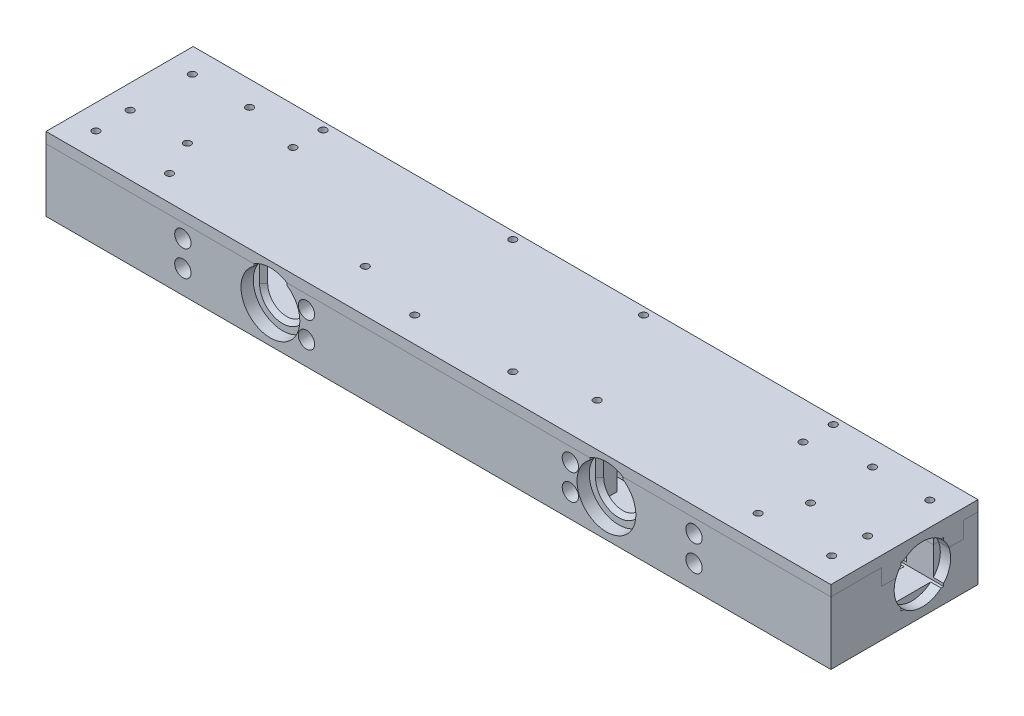
SolidWorks part; units mm, degrees
other "Bee-zerker Body Wedge"
other "Cam Body"
other "Cam Top Plate"
material "PLA/ABS"
ref_plane "Front Plane" through (0, 0, 0) normal (0, 0, 1) x (1, 0, 0)
ref_plane "Top Plane" through (0, 0, 0) normal (0, 1, 0) x (1, 0, 0)
ref_plane "Right Plane" through (0, 0, 0) normal (1, 0, 0) x (0, 0, -1)
sketch "Sketch1" plane through (0, 0, 0) normal (0, 1, 0) x (1, 0, 0)
  line L0 (-110.49, 0) -> (0, 0) construction
  line L1 (-152.4, -35.56) -> (152.4, -35.56)
  line L2 (-152.4, -35.56) -> (-152.4, 21.59)
  line L3 (-152.4, 21.59) -> (152.4, 21.59)
  line L4 (152.4, -35.56) -> (152.4, 21.59)
  line L5 (-152.4, -35.56) -> (152.4, 21.59) construction
  line L6 (-152.4, 21.59) -> (152.4, -35.56) construction
  line L11 (0, 0) -> (0, -6.985) construction
  line L12 (-65.25, 10.79) -> (-65.25, -35.56) construction
  line L13 (-110.49, 0) -> (-171.45, 0) construction
  line L14 (-110.49, -10.9728) -> (-152.4, -10.9728)
  line L15 (-110.49, -10.9728) -> (-110.49, 10.9728)
  line L16 (-110.49, 10.9728) -> (-152.4, 10.9728)
  line L17 (-152.4, -10.9728) -> (-152.4, 10.9728)
  line L18 (-110.49, -10.9728) -> (-152.4, 10.9728) construction
  line L19 (-110.49, 10.9728) -> (-152.4, -10.9728) construction
  line L20 (-45.725, -0.1905) -> (7.9198, -0.1905)
  line L21 (-45.725, -0.1905) -> (-45.725, 16.8275)
  line L22 (-45.725, 16.8275) -> (7.9198, 16.8275)
  line L23 (7.9198, -0.1905) -> (7.9198, 16.8275)
  line L24 (-45.725, -0.1905) -> (7.9198, 16.8275) construction
  line L25 (-45.725, 16.8275) -> (7.9198, -0.1905) construction
  line L26 (-95.25, 10.79) -> (-55.25, 10.79)
  line L27 (-95.25, 10.79) -> (-95.25, -29.21)
  line L28 (-95.25, -29.21) -> (-55.25, -29.21)
  line L29 (-55.25, 10.79) -> (-55.25, -29.21)
  line L30 (-95.25, 10.79) -> (-55.25, -29.21) construction
  line L31 (-95.25, -29.21) -> (-55.25, 10.79) construction
  point P0 (0, -6.985)
  point P12 (-75.25, -9.21)
  point P13 (-131.445, 0)
  point P19 (-18.9026, 8.3185)
  dimension "D1" = 304.8
  dimension "D2" = 57.15
  dimension "D3" = 21.59
  dimension "D4" = 40
  dimension "D5" = 17.018
  dimension "D6" = 41.91
  dimension "D7" = 21.9456
  dimension "D8" = 19.05
  dimension "D9" = 53.6448
  dimension "D10" = 40
  dimension "D11" = 57.15
  dimension "D12" = 6.35
  dimension "D13" = 4.7625
  dimension "D14" = 9.525
  dimension "D15" = 10
sketch "Sketch2" plane through (0, 0, 0) normal (1, 0, 0) x (0, 0, -1)
  line L0 (-35.56, 11.1125) -> (-35.56, 39.6875)
  line L1 (-35.56, 39.6875) -> (21.59, 39.6875)
  line L2 (21.59, 39.6875) -> (21.59, 11.1125)
  line L3 (21.59, 11.1125) -> (-35.56, 11.1125)
  line L4 (-53.2447, 0) -> (-13.764, 0) construction
  line L5 (0, 25.4) -> (21.59, 25.4) construction
  line L6 (-35.56, 25.4) -> (0, 25.4) construction
  line L7 (-32.5269, 35.56) -> (49967.4731, 35.56) construction
  line L8 (-34.7846, 15.24) -> (49965.2154, 15.24) construction
  line L9 (21.59, 35.56) -> (0, 25.4) construction
  line L10 (0, 25.4) -> (21.59, 15.24) construction
  line L12 (-120.0634, 50.8) -> (-69.9767, 50.8) construction
  circle A0 centre (0, 25.4) radius 25.4
  circle A2 centre (0, 25.4) radius 10.9728
  point P9 (10.9728, 25.4)
  dimension "D1" = 50.8
  dimension "D2" = 28.575
  dimension "D3" = 20.32
sketch "Sketch3" plane through (0, 0, 0) normal (1, 0, 0) x (0, 0, -1)
  line L0 (-35.56, 11.1125) -> (-35.56, 39.6875)
  line L1 (-35.56, 39.6875) -> (21.59, 39.6875)
  line L2 (21.59, 39.6875) -> (21.59, 11.1125)
  line L3 (21.59, 11.1125) -> (-35.56, 11.1125)
extrude "Boss-Extrude1" add sketch "Sketch3" along normal up to vertex (152.4 mm away) and the other way up to vertex (152.4 mm away) up to point (152.4, 0, -21.59) other way up to point (-152.4, 0, -21.59)
sketch "Sketch6" plane through (152.4, 0, 0) normal (1, 0, 0) x (0, 0, -1)
  line L1 (-8.255, 33.655) -> (8.255, 33.655)
  line L2 (-8.255, 33.655) -> (-8.255, 17.145)
  line L3 (-8.255, 17.145) -> (8.255, 17.145)
  line L4 (8.255, 33.655) -> (8.255, 17.145)
  line L5 (-8.255, 33.655) -> (8.255, 17.145) construction
  line L6 (-8.255, 17.145) -> (8.255, 33.655) construction
  point P0 (0, 25.4)
  dimension "D1" = 16.51
extrude "Cut-Extrude2" cut sketch "Sketch6" against normal blind 16.9164
sketch "Sketch7" plane through (152.4, 0, 0) normal (1, 0, 0) x (0, 0, -1)
  circle A0 centre (0, 25.4) radius 10.9728 construction
  circle A1 centre (0, 25.4) radius 10.9728
extrude "Cut-Extrude3" cut sketch "Sketch7" against normal blind 4.0132
sketch "Sketch8" plane through (135.4836, 0, 0) normal (1, 0, 0) x (0, 0, -1)
  circle A0 centre (0, 25.4) radius 10.9728 construction
  circle A1 centre (0, 25.4) radius 10.9728
extrude "Cut-Extrude4" cut sketch "Sketch8" along normal blind 2.54
sketch "Sketch9" plane through (135.4836, 0, 0) normal (1, 0, 0) x (0, 0, -1)
  line L0 (7.7495, 32.0331) -> (7.7495, 18.7669)
  line L1 (-7.7495, 18.7669) -> (-7.7495, 32.0331)
  line L2 (-7.7495, 25.4) -> (7.7495, 25.4) construction
  arc A0 (7.7495, 32.0331) -> (-7.7495, 32.0331) centre (0, 25.4) ccw
  arc A1 (-7.7495, 18.7669) -> (7.7495, 18.7669) centre (0, 25.4) ccw
  dimension "D1" = 20.4013
  dimension "D2" = 15.4991
extrude "Cut-Extrude5" cut sketch "Sketch9" against normal blind 25.4
mirror "Mirror1" of "Cut-Extrude2", "Cut-Extrude3", "Cut-Extrude4", "Cut-Extrude5"
extrude "Cut-Extrude6" cut sketch "Sketch10" against normal up to surface (110.0836 mm away)
sketch "Sketch10" plane through (110.0836, 0, 0) normal (1, 0, 0) x (0, 0, -1)
  line L1 (-9.525, 33.1495) -> (9.525, 33.1495)
  line L2 (-9.525, 33.1495) -> (-9.525, 17.6505)
  line L3 (-9.525, 17.6505) -> (9.525, 17.6505)
  line L4 (9.525, 33.1495) -> (9.525, 17.6505)
  line L5 (-9.525, 33.1495) -> (9.525, 17.6505) construction
  line L6 (-9.525, 17.6505) -> (9.525, 33.1495) construction
  point P0 (0, 25.4)
  dimension "D1" = 19.05
  dimension "D2" = 15.4991
sketch "Sketch11" plane through (0, 0, 0) normal (1, 0, 0) x (0, 0, -1)
  line L0 (-35.56, 39.6875) -> (-35.56, 11.1125) construction
  line L1 (21.59, 39.6875) -> (-35.56, 39.6875) construction
  line L2 (-35.56, 35.56) -> (-15.875, 35.56)
  line L3 (-15.875, 35.56) -> (-15.875, 29.21)
  line L4 (-15.875, 29.21) -> (0, 29.21)
  line L5 (15.875, 29.21) -> (15.875, 35.56)
  line L6 (15.875, 35.56) -> (21.59, 35.56)
  line L9 (0, 11.1125) -> (0, 39.6875) construction
  line L10 (-35.56, 11.1125) -> (21.59, 11.1125) construction
  line L12 (0, 29.21) -> (15.875, 29.21)
  line L13 (-35.56, 11.1125) -> (-35.56, 39.6875) construction
  line L14 (-200032.5269, 35.56) -> (249967.4731, 35.56) construction
  dimension "D1" = 10.4775
  dimension "D4" = 15.875
split "Split1" trim tools "Sketch11" bodies to split 113 resulting bodies 178 179
sketch "Sketch13" plane through (0, 11.1125, 0) normal (0, 1, 0) x (1, 0, 0)
  line L1 (-102.87, -15.875) -> (-102.87, 10.79)
  line L3 (-110.0836, 15.875) -> (110.0836, 15.875)
  line L5 (-102.87, 10.79) -> (-95.25, 10.79)
  line L7 (110.0836, 15.875) -> (110.0836, -15.875)
  line L8 (-152.4, -15.875) -> (152.4, -15.875) construction
  line L10 (-152.4, -15.875) -> (152.4, -15.875) construction
  line L12 (-95.25, 10.79) -> (-95.25, -29.21)
  line L16 (-110.0836, -15.875) -> (-110.0836, 15.875)
  line L18 (-110.0836, 7.7495) -> (-110.0836, -7.7495) construction
  line L19 (-152.4, 15.875) -> (152.4, 15.875) construction
  line L21 (-55.25, -29.21) -> (-55.25, 10.79)
  line L23 (-55.25, 10.79) -> (-47.63, 10.79)
  line L24 (-110.0836, -15.875) -> (-102.87, -15.875)
  line L25 (0, -15.875) -> (0, 0) construction
  line L27 (-47.63, 10.79) -> (-47.63, -15.875)
  line L28 (-95.25, -29.21) -> (-55.25, -29.21)
  line L29 (-47.63, -15.875) -> (47.63, -15.875)
  line L30 (47.63, -15.875) -> (47.63, 10.79)
  line L31 (47.63, 10.79) -> (55.25, 10.79)
  line L32 (55.25, 10.79) -> (55.25, -29.21)
  line L33 (95.25, -29.21) -> (95.25, 10.79)
  line L35 (95.25, 10.79) -> (102.87, 10.79)
  line L36 (102.87, 10.79) -> (102.87, -15.875)
  line L37 (55.25, -29.21) -> (95.25, -29.21)
  line L38 (102.87, -15.875) -> (110.0836, -15.875)
  line L39 (110.0836, -7.7495) -> (110.0836, 7.7495) construction
  line L40 (-152.4, -15.875) -> (152.4, -15.875) construction
  line L41 (-95.25, 10.79) -> (-95.25, -29.21) construction
  dimension "D1" = 7.62
extrude "Cut-Extrude7" cut sketch "Sketch13" along normal up to surface (20.32 mm away) from vertex at 4.1275 up to face at (0, 35.56, 25.7175) starting at point (0, 15.24, -21.59)
sketch "Sketch15" plane through (0, 0, 35.56) normal (0, 0, 1) x (1, 0, 0)
  line L0 (-95.25, 15.24) -> (-55.25, 15.24) construction
  line L1 (-95.25, 15.24) -> (-55.25, 15.24) construction
  line L2 (-71.7, 25.24) -> (-71.7, 35.56)
  line L3 (152.4, 35.56) -> (-152.4, 35.56) construction
  line L4 (-71.7, 35.56) -> (-58.8, 35.56)
  line L5 (-58.8, 35.56) -> (-58.8, 25.24)
  arc A0 (-71.7, 25.24) -> (-58.8, 25.24) centre (-65.25, 25.24) ccw
  arc A1 (-58.8, 25.24) -> (-71.7, 25.24) centre (-65.25, 25.24) ccw construction
  dimension "D1" = 12.9
  dimension "D2" = 10
extrude "Cut-Extrude8" cut sketch "Sketch15" against normal up to next (6.35 mm away)
sketch "Sketch16" plane through (0, 35.56, 0) normal (0, 1, 0) x (1, 0, 0)
  line L0 (-95.25, 10.79) -> (-95.25, -29.21) construction
  line L1 (-95.25, -21.49) -> (-102.4, -21.49)
  line L2 (-95.25, -21.49) -> (-95.25, -16.41)
  line L3 (-95.25, -16.41) -> (-102.4, -16.41)
  line L4 (-102.4, -21.49) -> (-102.4, -16.41)
  line L5 (-95.25, -21.49) -> (-102.4, -16.41) construction
  line L6 (-95.25, -16.41) -> (-102.4, -21.49) construction
  line L7 (-55.25, 10.79) -> (-55.25, -29.21) construction
  line L8 (-55.25, -21.49) -> (-48.1, -21.49)
  line L9 (-55.25, -21.49) -> (-55.25, -16.41)
  line L10 (-55.25, -16.41) -> (-48.1, -16.41)
  line L11 (-48.1, -21.49) -> (-48.1, -16.41)
  line L12 (-55.25, -21.49) -> (-48.1, -16.41) construction
  line L13 (-55.25, -16.41) -> (-48.1, -21.49) construction
  line L14 (-95.25, 10.79) -> (-55.25, 10.79) construction
  point P4 (-98.825, -18.95)
  point P11 (-51.675, -18.95)
  dimension "D1" = 27.2
  dimension "D2" = 7.15
  dimension "D3" = 5.08
extrude "Cut-Extrude9" cut sketch "Sketch16" against normal up to surface (20.32 mm away) up to face at (0, 15.24, 3.9175)
sketch "Sketch17" plane through (0, 29.21, 0) normal (0, 1, 0) x (1, 0, 0)
  line L1 (-102.87, -15.875) -> (-95.25, -15.875)
  line L2 (-102.87, -15.875) -> (-102.87, 10.79)
  line L3 (-102.87, 10.79) -> (-95.25, 10.79)
  line L4 (-95.25, -15.875) -> (-95.25, 10.79)
  line L5 (-102.87, -15.875) -> (-95.25, 10.79) construction
  line L6 (-102.87, 10.79) -> (-95.25, -15.875) construction
  line L7 (-47.63, -15.875) -> (-55.25, -15.875)
  line L8 (-47.63, -15.875) -> (-47.63, 10.79)
  line L9 (-47.63, 10.79) -> (-55.25, 10.79)
  line L10 (-55.25, -15.875) -> (-55.25, 10.79)
  line L11 (-47.63, -15.875) -> (-55.25, 10.79) construction
  line L12 (-47.63, 10.79) -> (-55.25, -15.875) construction
  point P4 (-99.06, -2.5425)
  point P11 (-51.44, -2.5425)
extrude "Boss-Extrude2" add sketch "Sketch17" along normal up to surface (6.35 mm away) up to face at (12.2143, 35.56, 23.3757)
sketch "Sketch18" plane through (0, 15.24, 0) normal (0, 1, 0) x (1, 0, 0)
  line L0 (110.0836, 15.875) -> (-110.0836, 15.875) construction
  line L1 (-102.87, 10.79) -> (-47.63, 10.79)
  line L2 (-102.87, 10.79) -> (-102.87, 15.875)
  line L3 (-102.87, 15.875) -> (-47.63, 15.875)
  line L4 (-47.63, 10.79) -> (-47.63, 15.875)
  line L5 (-102.87, 10.79) -> (-47.63, 15.875) construction
  line L6 (-102.87, 15.875) -> (-47.63, 10.79) construction
  line L7 (-55.25, 10.79) -> (-47.63, 10.79) construction
  line L8 (-55.25, 10.79) -> (-47.63, 10.79) construction
  point P4 (-75.25, 13.3325)
extrude "Boss-Extrude3" add sketch "Sketch18" along normal blind 9.525
sketch "Sketch19" plane through (-55.25, 0, 0) normal (-1, 0, 0) x (0, 0, 1)
  line L0 (-10.79, 21.59) -> (-2.79, 21.59)
  line L1 (-10.79, 24.765) -> (-10.79, 15.24) construction
  line L2 (-2.79, 21.59) -> (-2.79, 29.21)
  line L3 (-2.79, 29.21) -> (-10.79, 29.21)
  line L5 (-10.79, 29.21) -> (-10.79, 21.59)
  line L6 (16.41, 15.24) -> (-10.79, 15.24) construction
  line L8 (16.41, 25.4) -> (-2.79, 25.4) construction
  line L9 (16.41, 15.24) -> (16.41, 35.56) construction
  dimension "D1" = 6.35
  dimension "D3" = 8
extrude "Cut-Extrude10" cut sketch "Sketch19" against normal up to surface (7.62 mm away) up to face at (-47.63, 32.385, 2.5425)
sketch "Sketch20" plane through (0, 0, 35.56) normal (0, 0, 1) x (1, 0, 0)
  line L0 (-55.25, 15.24) -> (-48.1, 15.24) construction
  line L1 (-48.1, 15.24) -> (-48.1, 35.56) construction
  line L2 (-48.1, 35.56) -> (-55.25, 35.56) construction
  line L3 (-55.25, 35.56) -> (-55.25, 15.24) construction
  line L4 (-102.4, 15.24) -> (-95.25, 15.24) construction
  line L5 (-95.25, 15.24) -> (-95.25, 35.56) construction
  line L6 (-95.25, 35.56) -> (-102.4, 35.56) construction
  line L7 (-102.4, 35.56) -> (-102.4, 15.24) construction
  line L8 (-55.25, 15.24) -> (-48.1, 15.24) construction
  line L9 (-48.1, 15.24) -> (-48.1, 35.56) construction
  line L10 (-48.1, 35.56) -> (-55.25, 35.56) construction
  line L11 (-55.25, 35.56) -> (-55.25, 15.24) construction
  line L12 (-102.4, 15.24) -> (-95.25, 15.24) construction
  line L13 (-95.25, 15.24) -> (-95.25, 35.56) construction
  line L14 (-95.25, 35.56) -> (-102.4, 35.56) construction
  line L15 (-102.4, 35.56) -> (-102.4, 15.24) construction
  line L16 (-99.25, 20.24) -> (-99.25, 30.24) construction
  line L17 (-51.25, 20.24) -> (-51.25, 30.24) construction
  line L18 (-99.25, 25.24) -> (-95.25, 25.24) construction
  line L20 (-95.25, 25.24) -> (-65.25, 25.24) construction
  line L21 (-65.25, 25.24) -> (-55.25, 25.24) construction
  line L22 (-55.25, 25.24) -> (-51.25, 25.24) construction
  circle A0 centre (-99.25, 20.24) radius 3.175
  circle A1 centre (-99.25, 30.24) radius 3.175
  circle A2 centre (-51.25, 20.24) radius 3.175
  circle A3 centre (-51.25, 30.24) radius 3.175
  circle A4 centre (-65.25, 25.24) radius 6.45 construction
  circle A5 centre (-65.25, 25.24) radius 6.45 construction
  dimension "D2" = 6.35
  dimension "D1" = 4
  dimension "D3" = 10
extrude "Cut-Extrude11" cut sketch "Sketch20" against normal up to surface (19.15 mm away) up to face at (-98.825, 25.4, 16.41)
sketch "Sketch21" plane through (0, 0, 16.41) normal (0, 0, 1) x (1, 0, 0)
  circle A0 centre (-99.25, 30.24) radius 1.397
  circle A1 centre (-99.25, 20.24) radius 1.397
  circle A2 centre (-51.25, 20.24) radius 1.397
  circle A3 centre (-51.25, 30.24) radius 1.397
  dimension "D1" = 2.794
extrude "Cut-Extrude12" cut sketch "Sketch21" against normal blind 25.4
sketch "Sketch28" plane through (0, 0, 35.56) normal (0, 0, 1) x (1, 0, 0)
  circle A0 centre (-65.25, 25.24) radius 11.43
  dimension "D1" = 22.86
extrude "Cut-Extrude16" cut sketch "Sketch28" against normal blind 4.7625
mirror "Mirror2" about plane through (0, 0, 0) normal (1, 0, 0) of "Cut-Extrude16", "Cut-Extrude12", "Cut-Extrude11", "Cut-Extrude10", "Boss-Extrude3", "Boss-Extrude2", "Cut-Extrude9", "Cut-Extrude8"
sketch "Sketch23" plane through (0, 35.56, 0) normal (0, 1, 0) x (1, 0, 0)
  line L0 (-102.87, -15.875) -> (-102.87, 15.875) construction
  line L1 (-110.0836, -15.875) -> (-102.87, -15.875)
  line L2 (-110.0836, -15.875) -> (-110.0836, -9.525)
  line L3 (-110.0836, -9.525) -> (-102.87, -9.525)
  line L4 (-102.87, -15.875) -> (-102.87, -9.525)
  line L5 (-110.0836, -15.875) -> (-102.87, -9.525) construction
  line L6 (-110.0836, -9.525) -> (-102.87, -15.875) construction
  line L7 (102.87, -15.875) -> (102.87, 10.79) construction
  line L8 (110.0836, -15.875) -> (102.87, -15.875)
  line L9 (110.0836, -15.875) -> (110.0836, -9.525)
  line L10 (110.0836, -9.525) -> (102.87, -9.525)
  line L11 (102.87, -15.875) -> (102.87, -9.525)
  line L12 (110.0836, -15.875) -> (102.87, -9.525) construction
  line L13 (110.0836, -9.525) -> (102.87, -15.875) construction
  point P4 (-106.4768, -12.7)
  point P12 (106.4768, -12.7)
  dimension "D1" = 9.525
extrude "Boss-Extrude5" add sketch "Sketch23" against normal up to surface (20.32 mm away) up to face at (107.6791, 15.24, 0)
sketch "Sketch24" plane through (0, 35.56, 0) normal (0, -1, 0) x (1, 0, 0)
  line L0 (-152.4, -15.875) -> (-110.0836, -15.875) construction
  line L1 (-102.87, -10.79) -> (-47.63, -10.79)
  line L2 (-102.87, -10.79) -> (-102.87, -15.875)
  line L3 (-102.87, -15.875) -> (-47.63, -15.875)
  line L4 (-47.63, -10.79) -> (-47.63, -15.875)
  line L5 (-102.87, -10.79) -> (-47.63, -15.875) construction
  line L6 (-102.87, -15.875) -> (-47.63, -10.79) construction
  line L8 (47.63, -10.79) -> (102.87, -10.79)
  line L9 (47.63, -10.79) -> (47.63, -15.875)
  line L10 (47.63, -15.875) -> (102.87, -15.875)
  line L11 (102.87, -10.79) -> (102.87, -15.875)
  line L12 (47.63, -10.79) -> (102.87, -15.875) construction
  line L13 (47.63, -15.875) -> (102.87, -10.79) construction
  point P4 (-75.25, -13.3325)
  point P14 (75.25, -13.3325)
extrude "Boss-Extrude6" add sketch "Sketch24" along normal blind 3.175
sketch "Sketch25" plane through (0, 29.21, 0) normal (0, -1, 0) x (1, 0, 0)
  line L1 (-102.87, -10.79) -> (102.87, -10.79)
  line L2 (-102.87, -10.79) -> (-102.87, 15.875)
  line L3 (-102.87, 15.875) -> (102.87, 15.875)
  line L4 (102.87, -10.79) -> (102.87, 15.875)
  line L5 (-102.87, -10.79) -> (102.87, 15.875) construction
  line L6 (-102.87, 15.875) -> (102.87, -10.79) construction
  point P4 (0, 2.5425)
extrude "Cut-Extrude13" cut sketch "Sketch25" against normal up to surface (6.35 mm away) up to face at (0, 35.56, 1.7463)
sketch "Sketch26" plane through (0, 39.6875, 0) normal (0, 1, 0) x (1, 0, 0)
  line L0 (-142.875, -35.56) -> (-142.875, -25.7175) construction
  line L1 (152.4, -35.56) -> (-152.4, -35.56) construction
  line L2 (-142.875, -25.7175) -> (-142.875, -15.875) construction
  line L3 (-142.875, -25.7175) -> (-114.3, -25.7175) construction
  line L4 (-142.875, -25.7175) -> (-152.4, -25.7175) construction
  line L5 (-152.4, 21.59) -> (-152.4, -35.56) construction
  line L6 (-152.4, -15.875) -> (-110.0836, -15.875) construction
  line L7 (-95.25, -21.49) -> (-95.25, -29.21) construction
  line L8 (-143.2052, 8.255) -> (-143.2052, 12.065) construction
  line L9 (-148.3868, 8.255) -> (-138.0236, 8.255) construction
  line L10 (-143.2052, 12.065) -> (-143.2052, 15.875) construction
  line L11 (-152.4, 15.875) -> (152.4, 15.875) construction
  line L12 (-143.2052, -8.255) -> (-143.2052, -12.065) construction
  line L13 (-138.0236, -8.255) -> (-148.3868, -8.255) construction
  line L14 (-143.2052, -12.065) -> (-143.2052, -15.875) construction
  line L15 (-152.4, -15.875) -> (-110.0836, -15.875) construction
  line L16 (-143.2052, -12.065) -> (-120.9802, -12.065) construction
  line L17 (-143.2052, 12.065) -> (-120.9802, 12.065) construction
  line L18 (-99.06, 10.79) -> (-99.06, 6.98) construction
  line L19 (-102.87, 10.79) -> (-95.25, 10.79) construction
  line L20 (-99.06, 6.98) -> (-95.25, 6.98) construction
  line L21 (-95.25, -16.41) -> (-95.25, 10.79) construction
  line L22 (-99.06, 6.98) -> (-102.87, 6.98) construction
  line L23 (-102.87, -9.525) -> (-102.87, 10.79) construction
  line L24 (-99.06, 15.875) -> (-99.06, 18.7325) construction
  line L25 (-99.06, 18.7325) -> (-99.06, 21.59) construction
  line L26 (-152.4, 21.59) -> (152.4, 21.59) construction
  line L27 (-99.06, 18.7325) -> (-25.4, 18.7325) construction
  line L28 (-48.1, -18.95) -> (-45.025, -18.95) construction
  line L29 (-48.1, -21.49) -> (-48.1, -16.41) construction
  line L30 (-45.025, -18.95) -> (-45.025, -15.875) construction
  line L31 (-47.63, -15.875) -> (47.63, -15.875) construction
  circle A0 centre (-142.875, -25.7175) radius 1.397
  circle A1 centre (-114.3, -25.7175) radius 1.397
  circle A3 centre (-99.06, 6.98) radius 1.397
  circle A4 centre (-143.2052, 12.065) radius 1.397
  circle A5 centre (-120.9802, 12.065) radius 1.397
  circle A6 centre (-143.2052, -12.065) radius 1.397
  circle A7 centre (-120.9802, -12.065) radius 1.397
  circle A8 centre (-99.06, 18.7325) radius 1.397
  circle A10 centre (-25.4, 18.7325) radius 1.397
  circle A13 centre (-45.025, -18.95) radius 1.397
  circle A14 centre (-19.05, -25.7175) radius 1.397
  dimension "D1" = 2.794
  dimension "D2" = 9.525
  dimension "D3" = 19.05
  dimension "D4" = 22.225
  dimension "D5" = 25.4
  dimension "D6" = 19.05
extrude "Cut-Extrude14" cut sketch "Sketch26" against normal blind 25.4
mirror "Mirror3" about plane through (0, 0, 0) normal (1, 0, 0) of "Cut-Extrude14"
sketch "Sketch27" plane through (0, 35.56, 0) normal (0, 1, 0) x (1, 0, 0)
  line L0 (-40.01, -15.875) -> (-33.3425, -22.5425)
  line L1 (-47.63, -15.875) -> (47.63, -15.875) construction
  line L2 (-33.3425, -22.5425) -> (33.3425, -22.5425)
  line L3 (33.3425, -22.5425) -> (40.01, -15.875)
  line L4 (40.01, -15.875) -> (-40.01, -15.875)
  line L5 (0, -15.875) -> (0, 0) construction
  circle A0 centre (-19.05, -25.7175) radius 1.397 construction
  dimension "D1" = 3.175
  dimension "D2" = 45
  dimension "D3" = 7.62
extrude "Cut-Extrude15" cut sketch "Sketch27" against normal up to surface (20.32 mm away) up to face at (107.6791, 15.24, -2.1167)
chamfer "Chamfer1" distance 2.54 angle 45 6 edges at (65.25, 18.79, 30.7975) (-65.25, 18.79, 30.7975) (58.8, 29.9581, 30.7975) (71.7, 29.9581, 30.7975) (-58.8, 29.9581, 30.7975) (-71.7, 29.9581, 30.7975)
sketch "Sketch31" plane through (0, 0, 35.56) normal (0, 0, 1) x (1, 0, 0)
  line L0 (152.4, 35.56) -> (-152.4, 35.56) construction
  line L1 (-71.7, 35.56) -> (-58.8, 35.56)
  line L2 (-58.8, 34.6762) -> (-58.8, 35.56) construction
  line L3 (-47.63, 35.56) -> (-102.87, 35.56) construction
  line L4 (152.4, 35.56) -> (71.7, 35.56) construction
  line L5 (71.7, 35.56) -> (71.7, 34.6762) construction
  line L6 (58.8, 35.56) -> (71.7, 35.56)
  arc A0 (-71.7, 35.56) -> (-58.8, 35.56) centre (-65.25, 25.24) cw
  arc A1 (-74.24, 32.2987) -> (-56.26, 32.2987) centre (-65.25, 25.24) ccw construction
  arc A2 (58.8, 35.56) -> (71.7, 35.56) centre (65.25, 25.24) cw
  arc A3 (56.26, 32.2987) -> (74.24, 32.2987) centre (65.25, 25.24) ccw construction
  point P5 (0, 0)
extrude "Cut-Extrude17" cut sketch "Sketch31" against normal up to surface (6.35 mm away) up to face at (-68.5833, 29.4228, 29.21)
other "Save Bodies1"
